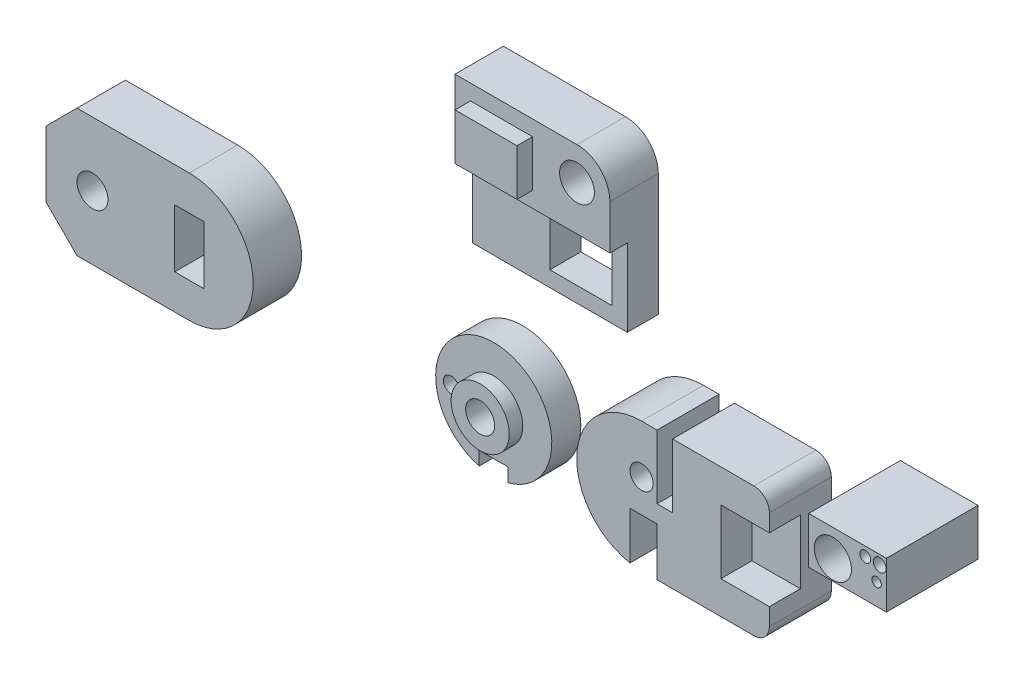
SolidWorks part; units mm, degrees
ref_plane "Alzado" through (0, 0, 0) normal (0, 0, 1) x (1, 0, 0)
ref_plane "Planta" through (0, 0, 0) normal (0, 1, 0) x (1, 0, 0)
ref_plane "Vista lateral" through (0, 0, 0) normal (1, 0, 0) x (0, 0, -1)
sketch "Croquis1" plane through (0, 0, 0) normal (0, 1, 0) x (1, 0, 0)
  line L0 (33.8203, -17.7774) -> (48.8203, -2.7774)
  line L1 (-21.1797, 22.5971) -> (8.8203, 22.5971)
  line L2 (-21.1797, 22.5971) -> (-21.1797, -7.7774)
  line L3 (-21.1797, -7.7774) -> (8.8203, -7.7774)
  line L4 (8.8203, 22.5971) -> (8.8203, -7.7774)
  line L5 (-31.1797, 32.2226) -> (23.8203, 32.2226)
  line L6 (-31.1797, 32.2226) -> (-31.1797, -17.7774)
  line L7 (-31.1797, -17.7774) -> (33.8203, -17.7774)
  line L8 (48.8203, 7.2226) -> (48.8203, -2.7774)
  line L11 (-137.0543, 86.4989) -> (-137.0543, 21.4989) construction
  line L12 (-117.0543, 86.4989) -> (-117.0543, 21.4989)
  line L13 (-157.0543, 86.4989) -> (-157.0543, 21.4989)
  line L14 (-136.7513, 86.4989) -> (-136.8704, 46.499) construction
  line L15 (-126.7514, 86.4691) -> (-126.8704, 46.4693)
  line L16 (-146.7513, 86.5286) -> (-146.8703, 46.5288)
  line L17 (126.5908, 199.0051) -> (151.5908, 199.0051)
  line L20 (-107.6871, 289.6873) -> (-161.8613, 289.6873)
  line L21 (-161.8613, 299.6873) -> (-161.8613, 289.6873)
  line L24 (-90.1456, 299.6873) -> (-161.8613, 299.6873)
  line L27 (-107.6871, 329.6873) -> (-161.8613, 329.6873)
  line L28 (-161.8613, 319.6873) -> (-161.8613, 329.6873)
  line L31 (-90.1456, 319.6873) -> (-161.8613, 319.6873)
  line L37 (76.5908, 211.891) -> (146.5908, 211.891)
  line L38 (51.5908, 186.891) -> (51.5908, 155.9069)
  line L39 (66.5908, 140.9069) -> (146.5908, 140.9069)
  line L40 (151.5908, 206.891) -> (151.5908, 199.0051)
  line L42 (151.5908, 174.7769) -> (151.5908, 145.9069)
  line L43 (126.5908, 174.7769) -> (151.5908, 174.7769)
  line L51 (366.5216, 153.1855) -> (310.2716, 153.1855)
  line L52 (310.2716, 224.3211) -> (310.2716, 153.1855)
  line L57 (510.6416, 11.6715) -> (610.6416, 11.6715)
  line L58 (510.6416, 11.6715) -> (510.6416, -88.3285)
  line L59 (510.6416, -88.3285) -> (610.6416, -88.3285)
  line L60 (610.6416, 11.6715) -> (610.6416, -88.3285)
  line L61 (610.6416, 11.6715) -> (710.6416, 11.6715)
  line L62 (610.6416, 11.6715) -> (610.6416, -88.3285)
  line L63 (610.6416, -88.3285) -> (710.6416, -88.3285)
  line L64 (710.6416, 11.6715) -> (710.6416, -88.3285)
  line L65 (510.6416, 11.6715) -> (550.6416, 11.6715)
  line L66 (510.6416, 11.6715) -> (510.6416, -38.3285)
  line L67 (510.6416, -38.3285) -> (550.6416, -38.3285)
  line L68 (550.6416, 11.6715) -> (550.6416, -38.3285)
  arc A0 (48.8203, 7.2226) -> (23.8203, 32.2226) centre (23.8203, 7.2226) ccw
  arc A1 (-117.0543, 86.4989) -> (-157.0543, 86.4989) centre (-137.0543, 86.4989) ccw
  arc A2 (-157.0543, 21.4989) -> (-117.0543, 21.4989) centre (-137.0543, 21.4989) ccw
  arc A3 (-126.7514, 86.4691) -> (-146.7513, 86.5286) centre (-136.7513, 86.4989) ccw
  arc A4 (-146.8703, 46.5288) -> (-126.8704, 46.4693) centre (-136.8704, 46.499) ccw
  arc A8 (-90.1456, 299.6873) -> (-90.1456, 319.6873) centre (-61.8613, 309.6873) ccw
  arc A10 (-107.6871, 289.6873) -> (-107.6871, 329.6873) centre (-61.8613, 309.6873) ccw
  arc A13 (76.5908, 211.891) -> (51.5908, 186.891) centre (76.5908, 186.891) ccw
  arc A14 (51.5908, 155.9069) -> (66.5908, 140.9069) centre (66.5908, 155.9069) ccw
  arc A15 (146.5908, 140.9069) -> (151.5908, 145.9069) centre (146.5908, 145.9069) ccw
  arc A16 (146.5908, 211.891) -> (151.5908, 206.891) centre (146.5908, 206.891) cw
  circle A17 centre (76.5908, 186.891) radius 15
  arc A18 (126.5908, 199.0051) -> (126.5908, 174.7769) centre (126.5908, 186.891) ccw
  arc A22 (366.5216, 153.1855) -> (310.2716, 224.3211) centre (362.0498, 207.4569) ccw
  circle A23 centre (362.0498, 207.4569) radius 18.75
  circle A24 centre (362.0498, 207.4569) radius 39.3 construction
  circle A25 centre (322.7498, 207.4569) radius 8.4
  circle A26 centre (362.0498, 207.4569) radius 39.3 construction
  circle A27 centre (334.2605, 235.2462) radius 8.4
  circle A28 centre (362.0498, 207.4569) radius 39.3 construction
  circle A29 centre (362.0498, 246.7569) radius 8.4
  circle A30 centre (362.0498, 207.4569) radius 39.3 construction
  circle A31 centre (389.8391, 235.2462) radius 8.4
  circle A32 centre (362.0498, 207.4569) radius 39.3 construction
  circle A33 centre (401.3498, 207.4569) radius 8.4
  circle A34 centre (362.0498, 207.4569) radius 39.3 construction
  circle A35 centre (389.8391, 179.6676) radius 8.4
  circle A36 centre (362.0498, 207.4569) radius 39.3 construction
  circle A37 centre (362.0498, 168.1569) radius 8.4
  circle A38 centre (362.0498, 207.4569) radius 39.3 construction
  circle A39 centre (334.2605, 179.6676) radius 8.4
  circle A42 centre (524.5413, 231.07) radius 42.0536 construction
  circle A43 centre (482.4876, 231.07) radius 7.585
  circle A44 centre (494.8049, 260.8064) radius 7.585
  circle A45 centre (524.5413, 273.1236) radius 7.585
  circle A46 centre (554.2777, 260.8064) radius 7.585
  circle A47 centre (566.5949, 231.07) radius 7.585
  circle A48 centre (554.2777, 201.3336) radius 7.585
  circle A49 centre (524.5413, 189.0164) radius 7.585
  circle A50 centre (494.8049, 201.3336) radius 7.585
  circle A51 centre (680.6416, -13.3285) radius 10
  circle A53 centre (680.6416, -63.3285) radius 10
  point P5 (48.8203, -17.7774)
  point P7 (-137.0543, 53.9989)
  point P21 (-136.8108, 66.499)
  point P85 (362.0498, 207.4569)
  point P104 (524.5413, 231.07)
  dimension "D4" = 25
  dimension "D12" = 10
  dimension "D14" = 60
  dimension "D15" = 100
  dimension "D17" = 25
  dimension "D18" = 15
  dimension "D19" = 5
  dimension "D20" = 5
  dimension "D21" = 80
  dimension "D24" = 78.6
  dimension "D25" = 16.8
  dimension "D33" = 30
  dimension "D35" = 50
  dimension "D1" = 30
  dimension "D2" = 40
  dimension "D3" = 80
  dimension "D5" = 10
  dimension "D6" = 10
  dimension "D7" = 40
  dimension "D9" = 65
  dimension "D10" = 20
  dimension "D11" = 40
  dimension "D13" = 20
  dimension "D16" = 100
  dimension "D22" = 50
  dimension "D23" = 25
  dimension "D28" = 100
  dimension "D29" = 100
  dimension "D30" = 100
  dimension "D31" = 40
  dimension "D32" = 50
  dimension "D34" = 25
  dimension "D26" = 8
  dimension "D27" = 8
sketch "Croquis3" plane through (0, 0, 0) normal (0, 0, 1) x (1, 0, 0)
  line L1 (50, 70) -> (113, 70)
  line L2 (50, 70) -> (50, 30)
  line L3 (50, 30) -> (130, 30)
  line L4 (130, 53) -> (130, 30)
  line L5 (58, 62) -> (90, 62)
  line L6 (58, 62) -> (58, 38)
  line L7 (58, 38) -> (90, 38)
  line L8 (90, 62) -> (90, 38)
  line L9 (50, 30) -> (130, 30)
  line L10 (50, 30) -> (50, -10)
  line L11 (50, -10) -> (130, -10)
  line L12 (130, 30) -> (130, -10)
  line L13 (90, 22) -> (122, 22)
  line L14 (90, 22) -> (90, -2)
  line L15 (90, -2) -> (122, -2)
  line L16 (122, 22) -> (122, -2)
  circle A0 centre (113, 53) radius 9
  arc A1 (113, 70) -> (130, 53) centre (113, 53) cw
  point P5 (392.6181, -4.5119)
  point P18 (0, 0)
  point P19 (0, 0)
  point P20 (0, 0)
  point P21 (456.9037, -11.9939)
  point P22 (0, 0)
  point P23 (0, 0)
  point P24 (0, 0)
  point P25 (0, 0)
  point P26 (392.6181, -84.5119)
  point P27 (392.6181, -84.5119)
  point P28 (392.6181, -84.5119)
  point P29 (0, 0)
  point P30 (392.6181, -84.5119)
  point P31 (0, 0)
  point P32 (392.3809, -44.9931)
  point P33 (391.9546, -44.981)
  point P34 (394.5788, -48.736)
  point P35 (418.6901, -46.7597)
  point P36 (406.4368, -45.1786)
  point P37 (243.5603, 9.343)
  point P38 (89.5712, -9.7632)
  point P40 (0, 0)
  point P41 (0, 0)
  point P42 (0, 0)
  point P43 (0, 0)
  point P44 (0, 0)
  dimension "D1" = 17
  dimension "D5" = 18
  dimension "D2" = 8
  dimension "D3" = 32
  dimension "D4" = 50
  dimension "D6" = 24
  dimension "D7" = 80
  dimension "D8" = 10
  dimension "D9" = 32
  dimension "D10" = 24
  dimension "D11" = 40
  dimension "D12" = 8
  dimension "D13" = 8
  dimension "D14" = 48
  dimension "D15" = 40
extrude "Saliente-Extruir4" add sketch "Croquis3" along normal blind 25 contours A1 L1 L2 L3 L4 A0 L5 L8 L7 L6 region at (91.9806, 49.1641, 0)
extrude "Saliente-Extruir5" add sketch "Croquis3<5>" along normal blind 33 contours L8 L5 L6 L7 | L6 L5 L8 L7 | L10 L9 L12 L11 region at (74, 50, 0)
sketch "Croquis3<5>" plane through (0, 0, 0) normal (0, 0, 1) x (1, 0, 0) same geometry as "Croquis3"
sketch "Croquis5" plane through (0, 0, 33) normal (0, 0, 1) x (1, 0, 0)
  line L1 (50, 30) -> (130, 30)
  line L2 (50, 30) -> (50, -10)
  line L3 (50, -10) -> (130, -10)
  line L4 (130, 30) -> (130, -10)
  point P6 (0, 0)
extrude "Cortar-Extruir1" cut sketch "Croquis5" against normal blind 17
extrude "Cortar-Extruir2" cut sketch "Croquis3<11>" along normal blind 30 contours L14 L15 L16 L13
sketch "Croquis3<11>" plane through (0, 0, 0) normal (0, 0, 1) x (1, 0, 0) same geometry as "Croquis3"
sketch "Croquis8" plane through (0, 0, 0) normal (0, 0, 1) x (1, 0, 0)
  line L4 (52.5, -102) -> (52.5, -109.0474)
  line L5 (67.5, -102) -> (67.5, -109.0474)
  line L6 (52.5, -102) -> (67.5, -102)
  arc A0 (67.5, -109.0474) -> (52.5, -109.0474) centre (60, -80) ccw
  circle A1 centre (60, -80) radius 15
  circle A2 centre (60, -80) radius 7.5
  circle A3 centre (38, -80) radius 4
  point P1 (60.2233, -82.0261)
  point P6 (0, 0)
  point P8 (0, 0)
  point P12 (0, 0)
  point P13 (59.3228, -88.3595)
  point P14 (52.1191, -80.0966)
  point P15 (0, 0)
  point P16 (59.8716, -79.0735)
  point P17 (39.2457, -79.0735)
  point P18 (62.1978, -94.5026)
  point P19 (61.1122, -90.0087)
  point P20 (59.4063, -79.0735)
  point P21 (0, 0)
  point P23 (0, 0)
  point P24 (61.975, -79.9509)
  point P25 (59.8391, -79.9509)
  point P26 (59.6877, -79.9509)
  point P27 (60, -79.7176)
  point P28 (60, -80)
  point P29 (60, -80)
  point P30 (60, -80)
  point P31 (60, -80)
  point P32 (60, -80)
  point P33 (38, -80)
  point P34 (38, -80)
  point P35 (60, -80)
  point P36 (60, -80)
  point P37 (60, -80)
  point P38 (60, -80)
  point P39 (60, -80)
  point P40 (60, -80)
  point P41 (60.4847, -80)
  dimension "D1" = 60
  dimension "D2" = 30
  dimension "D3" = 15
  dimension "D5" = 22
  dimension "D9" = 8
  dimension "D4" = 22
  dimension "D6" = 100
  dimension "D7" = 80
  dimension "D8" = 22
extrude "Saliente-Extruir6" add sketch "Croquis8" along normal blind 15 separate body contours A0 L4 L6 L5
extrude "Saliente-Extruir7" add sketch "Croquis8<4>" along normal blind 22 contours A1
sketch "Croquis8<4>" plane through (0, 0, 0) normal (0, 0, 1) x (1, 0, 0) same geometry as "Croquis8"
extrude "Cortar-Extruir5" cut sketch "Croquis8<6>" along normal blind 48 contours A3
sketch "Croquis8<6>" plane through (0, 0, 0) normal (0, 0, 1) x (1, 0, 0) same geometry as "Croquis8"
extrude "Cortar-Extruir6" cut sketch "Croquis8<7>" along normal blind 48 contours A2
sketch "Croquis8<7>" plane through (0, 0, 0) normal (0, 0, 1) x (1, 0, 0) same geometry as "Croquis8"
sketch "Croquis9" plane through (0, 0, 0) normal (0, 0, 1) x (1, 0, 0)
  line L0 (161.3648, -30) -> (153.3648, -30)
  line L1 (211.3648, -30) -> (169.3648, -30)
  line L2 (219.3648, -38) -> (219.3648, -89)
  line L3 (211.3648, -97) -> (161.3648, -97)
  line L4 (219.3648, -47) -> (194.3648, -47)
  line L5 (219.3648, -47) -> (219.3648, -80)
  line L6 (219.3648, -80) -> (194.3648, -80)
  line L7 (194.3648, -47) -> (194.3648, -80)
  line L9 (161.3648, -30) -> (161.3648, -63)
  line L10 (161.3648, -63) -> (169.3648, -63)
  line L11 (169.3648, -30) -> (169.3648, -63)
  line L14 (161.3648, -97) -> (161.3648, -72)
  line L15 (161.3648, -72) -> (147.3752, -72)
  line L16 (147.3752, -96.4602) -> (147.3752, -72)
  arc A1 (211.3648, -30) -> (219.3648, -38) centre (211.3648, -38) cw
  arc A2 (219.3648, -89) -> (211.3648, -97) centre (211.3648, -89) cw
  arc A3 (153.3648, -30) -> (147.3752, -96.4602) centre (153.3648, -63.5) ccw
  circle A4 centre (153.3648, -55) radius 6
  point P3 (0, 0)
  point P21 (0, 0)
  point P23 (204.1824, -54.5947)
  point P24 (204.1824, -60.8632)
  point P26 (120, -60.4931)
  point P27 (153.5, -55.4299)
  point P28 (0, 0)
  point P29 (153.5, -55.0877)
  point P31 (0, 0)
  dimension "D1" = 8
  dimension "D2" = 8
  dimension "D3" = 67
  dimension "D11" = 50
  dimension "D13" = 12
  dimension "D19" = 66
  dimension "D4" = 33
  dimension "D5" = 25
  dimension "D6" = 33
  dimension "D7" = 17
  dimension "D8" = 17
  dimension "D9" = 66
  dimension "D10" = 8
  dimension "D12" = 32.9602
  dimension "D14" = 58
  dimension "D15" = 14
  dimension "D16" = 25
  dimension "D17" = 30
  dimension "D18" = 120
  dimension "D20" = 25
extrude "Saliente-Extruir8" add sketch "Croquis9" along normal blind 32 separate body contours L0 A3 L16 L15 L14 L3 A2 L2 L6 L7 L4 A1 L1 L11 L10 L9 A4 region at (168.8723, -63.0964, 0)
extrude "Saliente-Extruir9" add sketch "Croquis9<3>" along normal blind 16 contours L7 L6 L5 L4
sketch "Croquis9<3>" plane through (0, 0, 0) normal (0, 0, 1) x (1, 0, 0) same geometry as "Croquis9"
sketch "Croquis10" plane through (0, 0, 0) normal (0, 0, 1) x (1, 0, 0)
  line L0 (-161.257, -58.8168) -> (-145.257, -42.8168)
  line L3 (-145.257, -42.8168) -> (-87.257, -42.8168)
  line L4 (-94.757, -60.8168) -> (-79.757, -60.8168)
  line L5 (-161.257, -58.8168) -> (-161.257, -92.8168)
  line L6 (-145.257, -108.8168) -> (-87.257, -108.8168)
  line L8 (-94.757, -60.8168) -> (-94.757, -90.8168)
  line L9 (-94.757, -90.8168) -> (-79.757, -90.8168)
  line L10 (-79.757, -60.8168) -> (-79.757, -90.8168)
  line L11 (-161.257, -92.8168) -> (-145.257, -108.8168)
  line L13 (-161.257, -92.8168) -> (-137.257, -92.8168)
  line L14 (-161.257, -92.8168) -> (-161.257, -58.8168)
  line L15 (-161.257, -58.8168) -> (-137.257, -58.8168)
  arc A2 (-87.257, -108.8168) -> (-87.257, -42.8168) centre (-87.257, -75.8168) ccw
  arc A3 (-137.257, -92.8168) -> (-137.257, -58.8168) centre (-137.257, -75.8168) ccw
  circle A4 centre (-137.257, -75.8168) radius 8
  point P0 (-161.257, -42.8168)
  point P2 (-161.257, -108.8168)
  point P13 (-145.257, -42.8168)
  point P18 (0, 0)
  point P20 (0, 0)
  dimension "D2" = 66
  dimension "D8" = 34
  dimension "D11" = 16
  dimension "D1" = 74
  dimension "D3" = 66
  dimension "D4" = 15
  dimension "D5" = 30
  dimension "D6" = 7.5
  dimension "D7" = 24
  dimension "D12" = 33
  dimension "D13" = 97.196
  dimension "D14" = 87.257
  dimension "D15" = 15
extrude "Saliente-Extruir11" add sketch "Croquis10" along normal blind 25 separate body contours L10 L4 L8 L9 | A3 L13 L11 L6 A2 L3 L0 L15 L4 L10 L9 L8 | L13 A3 L15 L5 A4 | A4 region at (-149.257, -59.3495, 0) region at (-102.2304, -75.8168, 0) region at (-87.257, -75.8168, 0) region at (-137.257, -75.8168, 0)
extrude "Cortar-Extruir7" cut sketch "Croquis10<4>" along normal blind 25 contours L8 L9 L10 L4
sketch "Croquis10<4>" plane through (0, 0, 0) normal (0, 0, 1) x (1, 0, 0) same geometry as "Croquis10"
extrude "Cortar-Extruir8" cut sketch "Croquis10<5>" along normal blind 25 contours A4
sketch "Croquis10<5>" plane through (0, 0, 0) normal (0, 0, 1) x (1, 0, 0) same geometry as "Croquis10"
sketch "Croquis13" plane through (0, 0, 0) normal (0, 0, -1) x (-1, 0, 0)
  line L0 (161.257, -58.8168) -> (137.257, -58.8168)
  line L1 (137.257, -92.8168) -> (161.257, -92.8168)
  line L2 (161.257, -92.8168) -> (175.7257, -74.2467)
  line L3 (175.7257, -74.2467) -> (161.257, -58.8168)
  arc A0 (137.257, -58.8168) -> (137.257, -92.8168) centre (137.257, -75.8168) ccw
extrude "Cortar-Extruir9" cut sketch "Croquis13" against normal blind 8.3333
sketch "Croquis14" plane through (0, 0, 0) normal (0, 0, 1) x (1, 0, 0)
  line L13 (295.131, -12.813) -> (255.0355, -12.813)
  line L14 (295.131, -12.813) -> (295.131, -36.9134)
  line L15 (295.131, -36.9134) -> (255.0355, -36.9134)
  line L16 (255.0355, -12.813) -> (255.0355, -36.9134)
  circle A0 centre (291.7135, -17.4989) radius 3.3142
  circle A1 centre (267.5114, -26.7899) radius 9.5923
  circle A2 centre (290.0939, -25.9083) radius 2.4178
  circle A3 centre (284.2272, -17.4989) radius 2.7887
extrude "Saliente-Extruir12" add sketch "Croquis14" along normal blind 47.3333 separate body
